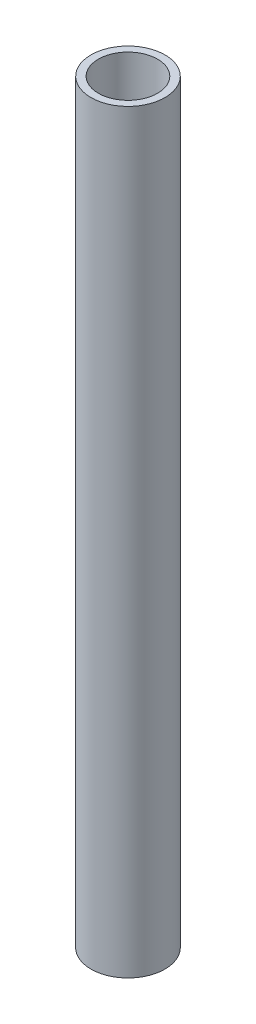
SolidWorks part; units mm, degrees
material "Сталь 08Х21Н5Т ГОСТ 5632-72"
ref_plane "Спереди" through (0, 0, 0) normal (0, 0, 1) x (1, 0, 0)
ref_plane "Сверху" through (0, 0, 0) normal (0, 1, 0) x (1, 0, 0)
ref_plane "Справа" through (0, 0, 0) normal (1, 0, 0) x (0, 0, -1)
other "Configuration Table"
sketch "Эскиз1" plane through (0, 0, 0) normal (0, 1, 0) x (1, 0, 0)
  circle A0 centre (0, 0) radius 4
  circle A1 centre (0, 0) radius 5
  dimension "D1" = 10
  dimension "D2" = 8
extrude "Бобышка-Вытянуть1" add sketch "Эскиз1" along normal blind 102
